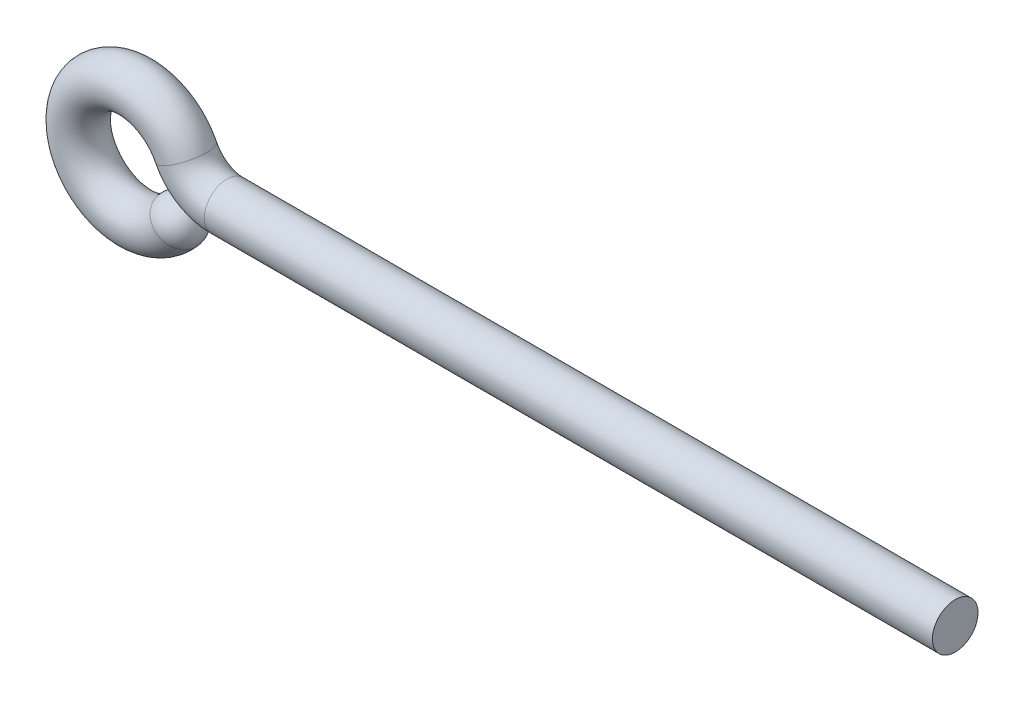
SolidWorks part; units mm, degrees
ref_plane "Front Plane" through (0, 0, 0) normal (0, 0, 1) x (1, 0, 0)
ref_plane "Top Plane" through (0, 0, 0) normal (0, 1, 0) x (1, 0, 0)
ref_plane "Right Plane" through (0, 0, 0) normal (1, 0, 0) x (0, 0, -1)
sketch "Sketch1" plane through (0, 0, 0) normal (0, 0, 1) x (1, 0, 0)
  line L0 (0, 0) -> (-1.9689, 0) construction
  line L1 (-6, 0) -> (-4.0849, -1.607) construction
  line L2 (-1.9689, 0) -> (0, 0)
  arc A0 (-3.7605, 1.1111) -> (-4.0849, -1.607) centre (-6, 0) ccw
  arc A1 (-1.9689, 0) -> (-3.7605, 1.1111) centre (-1.9689, 2) cw
  dimension "D2" = 2.5
  dimension "D1" = 2
  dimension "D3" = 40
sketch "Sketch3" plane through (0, 0, 0) normal (1, 0, 0) x (0, 0, -1)
  circle A0 centre (0, 0) radius 1
  dimension "D1" = 2
sweep "Sweep1" add profiles "Sketch3" path "Sketch1"
sketch "Sketch5" plane through (0, 0, 0) normal (1, 0, 0) x (0, 0, -1)
  circle A1 centre (0, 0) radius 1
  circle A2 centre (0, 0) radius 1
  dimension "D1" = 0
extrude "Boss-Extrude1" add sketch "Sketch5" along normal blind 30
dome "Dome1" faces to dome 1 distance 1 reverse direction no elliptical dome no face at (-4.0849, -1.607, -1) parameters "D1"=1
